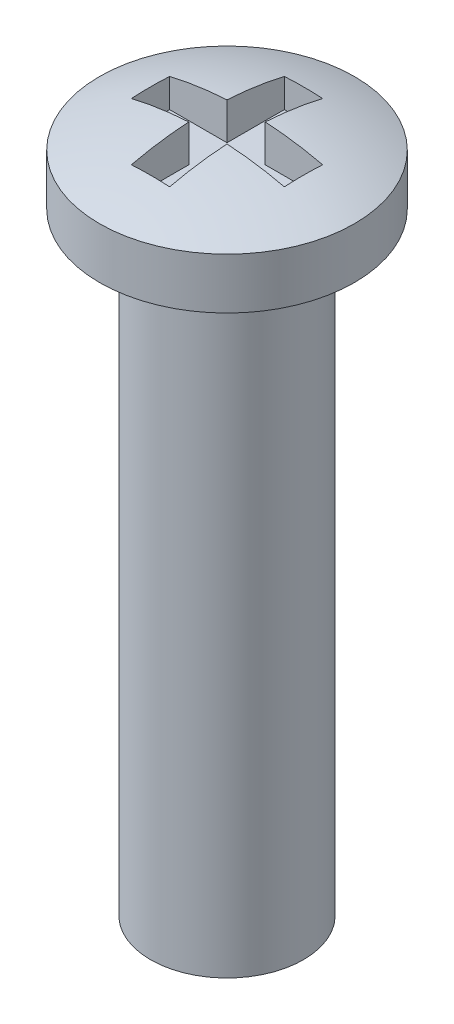
SolidWorks part; units mm, degrees
material "1023 Carbon Steel Sheet (SS)"
ref_plane "Front Plane" through (0, 0, 0) normal (0, 0, 1) x (1, 0, 0)
ref_plane "Top Plane" through (0, 0, 0) normal (0, 1, 0) x (1, 0, 0)
ref_plane "Right Plane" through (0, 0, 0) normal (1, 0, 0) x (0, 0, -1)
ref_plane "Top Plane1" through (0, 13.5, 0) normal (0, 1, 0) x (1, 0, 0)
sketch "Sketch1" plane through (0, 0, 0) normal (0, 1, 0) x (1, 0, 0)
  circle A0 centre (0, 0) radius 1.5
  dimension "D1" = 3
extrude "Boss-Extrude1" add sketch "Sketch1" along normal blind 12
sketch "Sketch2" plane through (0, 12, 0) normal (0, 1, 0) x (1, 0, 0)
  circle A0 centre (0, 0) radius 2.5
  dimension "D1" = 5
extrude "Boss-Extrude2" add sketch "Sketch2" along normal blind 1
dome "Dome1" faces to dome 1 distance 0.5 reverse direction no elliptical dome no face at (0, 13, 2.5) parameters "D1"=0.5
sketch "Sketch3" plane through (0, 13.5, 0) normal (0, 1, 0) x (1, 0, 0)
  line L0 (-2.5, 0) -> (2.5, 0) construction
  line L1 (0, 2.5) -> (0, -2.5) construction
  line L2 (-1.5, 0.375) -> (1.5, -0.375) construction
  line L3 (-1.5, 0.375) -> (1.5, 0.375)
  line L4 (-1.5, 0.375) -> (-1.5, -0.375)
  line L5 (-1.5, -0.375) -> (1.5, -0.375)
  line L6 (1.5, 0.375) -> (1.5, -0.375)
  line L7 (0.375, 1.5) -> (-0.375, -1.5) construction
  line L8 (-0.375, 1.5) -> (0.375, 1.5)
  line L9 (-0.375, 1.5) -> (-0.375, -1.5)
  line L10 (-0.375, -1.5) -> (0.375, -1.5)
  line L11 (0.375, 1.5) -> (0.375, -1.5)
  circle A0 centre (0, 0) radius 2.5 construction
  dimension "D1" = 1.5
  dimension "D2" = 1.5
  dimension "D3" = 0.75
  dimension "D4" = 0.75
extrude "Cut-Extrude1" cut sketch "Sketch3" against normal blind 0.75 contours L9 L3 L4 L5 | L11 L3 L9 L5 | L11 L8 L9 L3 | L3 L11 L5 L6 | L11 L5 L9 L10 region at (-0.9375, 13.5, 0) region at (0, 13.5, -0.9375) region at (0, 13.5, 0) region at (0.9375, 13.5, 0) region at (0, 13.5, 0.9375)
sketch "Sketch4" plane through (0, 0, 0) normal (0, -1, 0) x (1, 0, 0)
  point P0 (0, 0)
